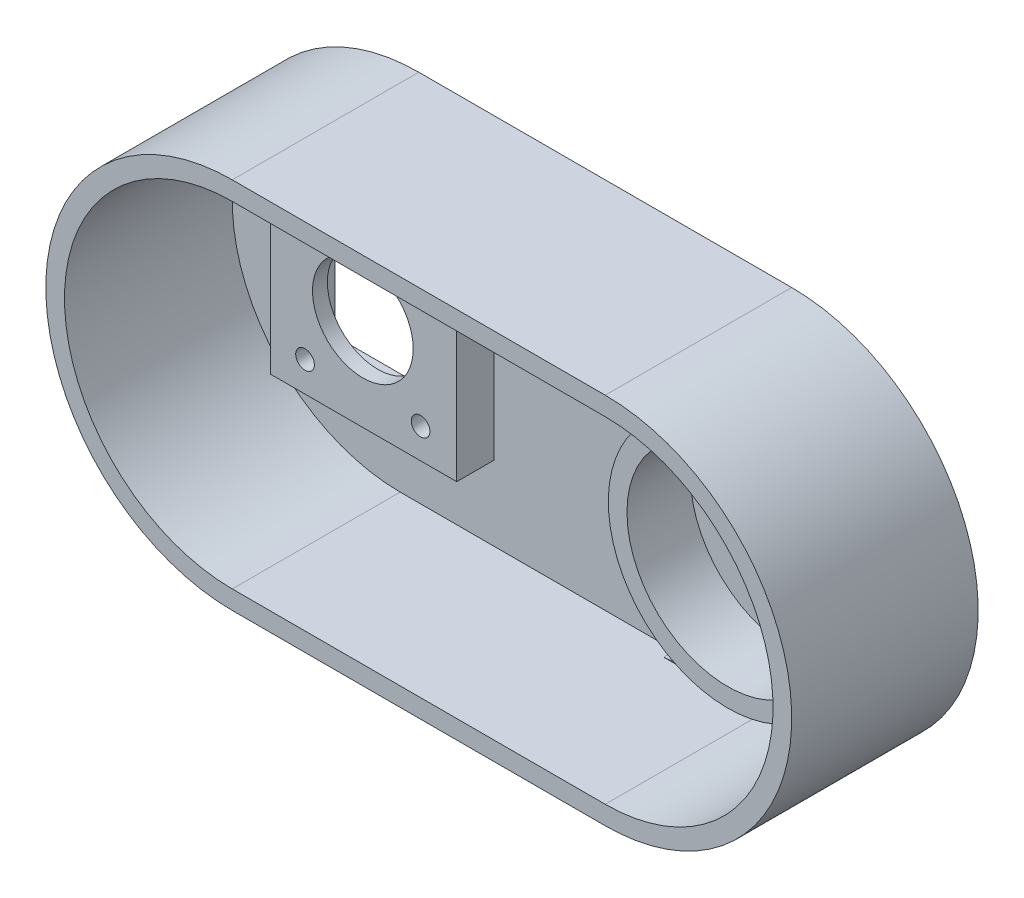
SolidWorks part; units mm, degrees
ref_plane "Front Plane" through (0, 0, 0) normal (0, 0, 1) x (1, 0, 0)
ref_plane "Top Plane" through (0, 0, 0) normal (0, 1, 0) x (1, 0, 0)
ref_plane "Right Plane" through (0, 0, 0) normal (1, 0, 0) x (0, 0, -1)
sketch "Sketch1" plane through (0, 0, 0) normal (0, 0, 1) x (1, 0, 0)
  line L0 (46.31, 0) -> (-53.69, 0) construction
  line L1 (46.31, -45) -> (-53.69, -45)
  line L2 (46.31, 45) -> (-53.69, 45)
  arc A0 (46.31, -45) -> (46.31, 45) centre (46.31, 0) ccw
  arc A1 (-53.69, 45) -> (-53.69, -45) centre (-53.69, 0) ccw
  point P3 (-3.69, 0)
  point P8 (-53.69, 0)
  dimension "D1" = 45
extrude "Extrude-Thin1" add sketch "Sketch1" along normal blind 50 thin contours L2 A1 L1 A0 thin type one direction wall 5
extrude "Boss-Extrude1" add sketch "Sketch1<3>" along normal blind 5 contours L2 A1 L1 A0 region at (-3.69, 0, 0)
sketch "Sketch1<3>" plane through (0, 0, 0) normal (0, 0, 1) x (1, 0, 0) same geometry as "Sketch1"
sketch "Sketch2" plane through (0, 0, 0) normal (0, 0, -1) x (-1, 0, 0)
  circle A0 centre (-51.1407, -2.2577) radius 12.5
  dimension "D1" = 25
sketch "Sketch4" plane through (0, 0, 5) normal (0, 0, 1) x (1, 0, 0)
  circle A0 centre (51.1407, -2.2577) radius 26.5
  dimension "D1" = 53
sketch "Sketch5" plane through (0, 0, 5) normal (0, 0, 1) x (1, 0, 0)
  circle A0 centre (51.1407, -2.2577) radius 32
  dimension "D1" = 64
extrude "Extrude-Thin4" add sketch "Sketch5" along normal blind 17 thin thin type one direction reverse wall 5
extrude "Cut-Extrude2" cut sketch "Sketch2" against normal through all contours A0
sketch "Sketch10" plane through (0, 0, 5) normal (0, 0, 1) x (1, 0, 0)
  line L0 (51.1407, 29.7423) -> (46.31, 45)
  line L1 (46.31, 45) -> (33.0788, 45)
  line L2 (46.31, 45) -> (-53.69, 45) construction
  line L3 (33.0788, 45) -> (40.9577, 28.0788)
  line L4 (51.1407, 29.7423) -> (41.321, 28.1984)
  line L5 (41.321, 28.1984) -> (40.9577, 28.0788)
  circle A0 centre (51.1407, -2.2577) radius 32 construction
extrude "Boss-Extrude4" add sketch "Sketch10" along normal blind 3
fillet "Fillet1" radius 10 1 edges
fillet "Fillet2" radius 10 1 edges at (51.1407, 29.7423, 6.5)
sketch "Sketch11" plane through (0, 0, 5) normal (0, 0, 1) x (1, 0, 0)
  line L0 (34.7565, -29.7452) -> (25.6637, -45)
  line L1 (46.31, -45) -> (-53.69, -45) construction
  line L2 (25.6637, -45) -> (38.4867, -45)
  line L3 (38.4867, -45) -> (41.405, -32.7408)
  line L4 (41.405, -32.7408) -> (34.7565, -29.7452)
  circle A0 centre (51.1407, -2.2577) radius 32 construction
extrude "Boss-Extrude5" add sketch "Sketch11" along normal blind 3
fillet "Fillet3" radius 10 1 edges at (38.4867, -45, 6.5)
fillet "Fillet4" radius 10 1 edges at (25.6637, -45, 6.5)
sketch "Sketch13" plane through (0, 0, 5) normal (0, 0, 1) x (1, 0, 0)
  line L0 (90.7057, -8.7247) -> (82.5015, -8.7247)
  line L1 (82.5015, -8.7247) -> (83.0847, 0)
  line L2 (83.0847, 0) -> (91.6675, 0)
  line L3 (91.6675, 0) -> (90.7057, -8.7247)
extrude "Boss-Extrude11" add sketch "Sketch13" along normal blind 3
fillet "Fillet6" radius 10 1 edges at (91.31, 0, 6.5)
fillet "Fillet7" radius 10 1 edges at (90.4561, -8.7247, 6.5)
sketch "Sketch14" plane through (0, 0, 5) normal (0, 0, 1) x (1, 0, 0)
  line L1 (-78.5075, -25) -> (-28.5075, -25)
  line L2 (-78.5075, -25) -> (-78.5075, 25)
  line L3 (-78.5075, 25) -> (-28.5075, 25)
  line L4 (-28.5075, -25) -> (-28.5075, 25)
  line L5 (-78.5075, -25) -> (-28.5075, 25) construction
  line L6 (-78.5075, 25) -> (-28.5075, -25) construction
  point P0 (-53.5075, 0)
  dimension "D1" = 50
  dimension "D2" = 50
extrude "Boss-Extrude12" add sketch "Sketch14" along normal blind 10
sketch "Sketch16" plane through (0, 0, 15) normal (0, 0, 1) x (1, 0, 0)
  line L0 (-53.69, 22.5) -> (-53.69, -22.5) construction
  line L1 (-76.19, -22.5) -> (-31.19, -22.5)
  line L2 (-76.19, -22.5) -> (-76.19, 22.5)
  line L3 (-76.19, 22.5) -> (-31.19, 22.5)
  line L4 (-31.19, -22.5) -> (-31.19, 22.5)
  line L5 (-76.19, -22.5) -> (-31.19, 22.5) construction
  line L6 (-76.19, 22.5) -> (-31.19, -22.5) construction
  circle A0 centre (-53.69, 0) radius 13.5
  circle A1 centre (-69.19, 14.0434) radius 2.5
  circle A4 centre (-69.19, -16.9566) radius 2.5
  circle A5 centre (-38.19, -16.9566) radius 2.5
  circle A6 centre (-38.19, 14.0434) radius 2.5
  point P0 (-53.69, 0)
  dimension "D3" = 27
  dimension "D4" = 5
  dimension "D1" = 45
  dimension "D2" = 45
  dimension "D5" = 31
  dimension "D6" = 31
extrude "Cut-Extrude5" cut sketch "Sketch16" against normal blind 25 from offset 4 offset against normal yes
extrude "Cut-Extrude6" cut sketch "Sketch16<2>" against normal through all contours A6 | A1 | A0 | A4 | A5 region at (-53.69, 0, 15) region at (-69.19, 14.0434, 15) region at (-69.19, -16.9566, 15) region at (-38.19, 14.0434, 15)
sketch "Sketch16<2>" plane through (0, 0, 15) normal (0, 0, 1) x (1, 0, 0) same geometry as "Sketch16"
